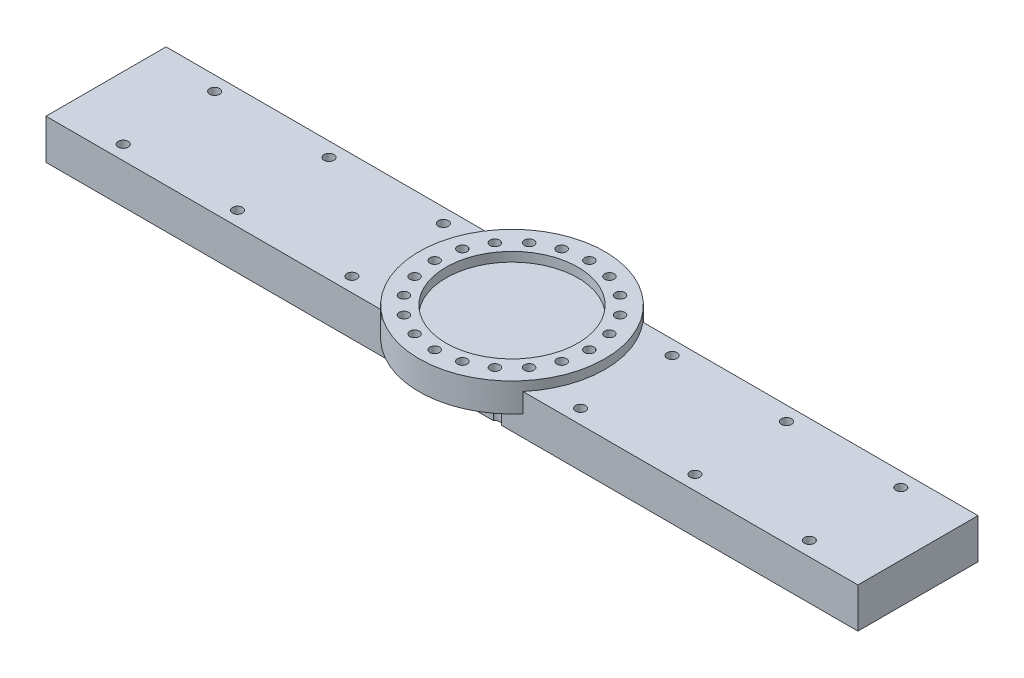
SolidWorks part; units mm, degrees
ref_plane "Front Plane" through (0, 0, 0) normal (0, 0, 1) x (1, 0, 0)
ref_plane "Top Plane" through (0, 0, 0) normal (0, 1, 0) x (1, 0, 0)
ref_plane "Right Plane" through (0, 0, 0) normal (1, 0, 0) x (0, 0, -1)
sketch "Sketch1" plane through (0, 0, 0) normal (0, 1, 0) x (1, 0, 0)
  line L0 (15.8996, 21.8839) -> (0, 0) construction
  line L1 (0, 0) -> (27.05, 0) construction
  circle A0 centre (0, 0) radius 27.05 construction
  circle A1 centre (15.8996, 21.8839) radius 1.675
  circle A2 centre (0, 0) radius 32.5
  circle A3 centre (21.8839, 15.8996) radius 1.675
  circle A4 centre (25.7261, 8.3589) radius 1.675
  circle A5 centre (27.05, 0) radius 1.675
  circle A6 centre (25.7261, -8.3589) radius 1.675
  circle A7 centre (21.8839, -15.8996) radius 1.675
  circle A8 centre (15.8996, -21.8839) radius 1.675
  circle A9 centre (8.3589, -25.7261) radius 1.675
  circle A10 centre (0, -27.05) radius 1.675
  circle A11 centre (-8.3589, -25.7261) radius 1.675
  circle A12 centre (-15.8996, -21.8839) radius 1.675
  circle A13 centre (-21.8839, -15.8996) radius 1.675
  circle A14 centre (-25.7261, -8.3589) radius 1.675
  circle A15 centre (-27.05, 0) radius 1.675
  circle A16 centre (-25.7261, 8.3589) radius 1.675
  circle A17 centre (-21.8839, 15.8996) radius 1.675
  circle A18 centre (-15.8996, 21.8839) radius 1.675
  circle A19 centre (-8.3589, 25.7261) radius 1.675
  circle A20 centre (0, 27.05) radius 1.675
  circle A21 centre (8.3589, 25.7261) radius 1.675
  point P49 (0, 0)
  dimension "D2" = 3.35
  dimension "D3" = 54.1
  dimension "D4" = 65
  dimension "D1" = 54
  dimension "D5" = 20
extrude "Boss-Extrude1" add sketch "Sketch1" along normal blind 10
sketch "Sketch2" plane through (0, 10, 0) normal (0, 1, 0) x (1, 0, 0)
  circle A0 centre (0, 0) radius 23.05
  dimension "D1" = 46.1
extrude "Cut-Extrude1" cut sketch "Sketch2" against normal blind 3.25
sketch "Sketch3" plane through (0, 0, 0) normal (0, -1, 0) x (1, 0, 0)
  line L0 (-142, 21) -> (142, 21)
  line L1 (-142, 21) -> (-142, -21)
  line L2 (-142, -21) -> (142, -21)
  line L3 (142, 21) -> (142, -21)
  line L4 (-120, 16) -> (120, 16) construction
  line L5 (-120, 16) -> (-120, -16) construction
  line L6 (-120, -16) -> (120, -16) construction
  line L7 (120, 16) -> (120, -16) construction
  circle A0 centre (-120, 16) radius 1.75
  circle A1 centre (-80, 16) radius 1.75
  circle A2 centre (-40, 16) radius 1.75
  circle A3 centre (0, 16) radius 1.75
  circle A4 centre (40, 16) radius 1.75
  circle A5 centre (80, 16) radius 1.75
  circle A6 centre (120, 16) radius 1.75
  circle A7 centre (120, -16) radius 1.75
  circle A8 centre (80, -16) radius 1.75
  circle A9 centre (40, -16) radius 1.75
  circle A10 centre (0, -16) radius 1.75
  circle A11 centre (-40, -16) radius 1.75
  circle A12 centre (-80, -16) radius 1.75
  circle A13 centre (-120, -16) radius 1.75
  point P35 (-120, 0)
  point P36 (-142, 0)
  point P57 (0, -21)
  dimension "D10" = 3.5
  dimension "D1" = 42
  dimension "D2" = 284
  dimension "D3" = 40
  dimension "D4" = 40
  dimension "D5" = 40
  dimension "D6" = 40
  dimension "D7" = 40
  dimension "D8" = 40
  dimension "D9" = 32
extrude "Boss-Extrude2" add sketch "Sketch3" against normal blind 6.75 and the other way blind 7.25
extrude "Cut-Extrude2" cut sketch "Sketch1<2>" against normal through all and the other way through all contours A18 | A20 | A21 | A1 | A8 | A9 | A10 | A11 | A19 | A3 | A4 | A5 | A6 | A7 | A12 | A13 | A14 | A15 | A16 | A17 region at (15.8996, 0, -21.8839) region at (15.8996, 0, 21.8839) region at (8.3589, 0, 25.7261) region at (0, 0, 27.05) region at (-8.3589, 0, 25.7261) region at (-15.8996, 0, -21.8839) region at (0, 0, -27.05) region at (8.3589, 0, -25.7261)
sketch "Sketch1<2>" plane through (0, 0, 0) normal (0, 1, 0) x (1, 0, 0) same geometry as "Sketch1"
